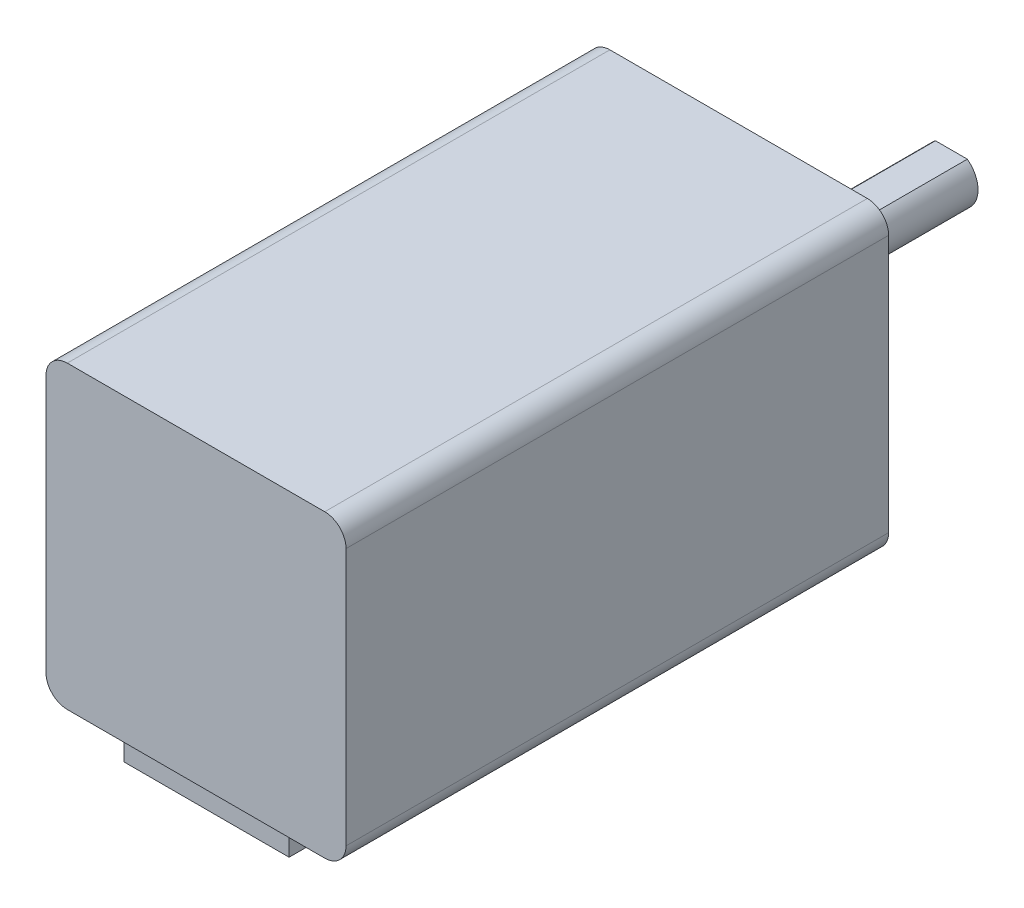
SolidWorks part; units mm, degrees
ref_plane "前视基准面" through (0, 0, 0) normal (0, 0, 1) x (1, 0, 0)
ref_plane "上视基准面" through (0, 0, 0) normal (0, 1, 0) x (1, 0, 0)
ref_plane "右视基准面" through (0, 0, 0) normal (1, 0, 0) x (0, 0, -1)
sketch "草图1" plane through (0, 0, 0) normal (0, 0, 1) x (1, 0, 0)
  line L0 (0, 0) -> (-46.9688, 0) construction
  line L1 (0, 0) -> (46.2703, 0) construction
  line L2 (0, 0) -> (0, -44.5864) construction
  line L3 (0, 0) -> (0, 48.8523) construction
  line L4 (-12.1, -14.1) -> (12.1, -14.1)
  line L5 (-14.1, -12.1) -> (-14.1, 12.1)
  line L6 (-12.1, 14.1) -> (12.1, 14.1)
  line L7 (14.1, -12.1) -> (14.1, 12.1)
  circle A0 centre (-11.5, 11.5) radius 1.25
  circle A1 centre (11.5, 11.5) radius 1.25
  circle A2 centre (-11.5, -11.5) radius 1.25
  circle A3 centre (11.5, -11.5) radius 1.25
  arc A4 (-12.1, -14.1) -> (-14.1, -12.1) centre (-12.1, -12.1) cw
  arc A5 (12.1, -14.1) -> (14.1, -12.1) centre (12.1, -12.1) ccw
  arc A6 (14.1, 12.1) -> (12.1, 14.1) centre (12.1, 12.1) ccw
  arc A7 (-14.1, 12.1) -> (-12.1, 14.1) centre (-12.1, 12.1) cw
  point P9 (14.1, 0)
  point P10 (-14.1, 0)
  point P11 (0, 14.1)
  point P12 (0, -14.1)
  point P23 (-14.1, -14.1)
  point P26 (14.1, -14.1)
  point P29 (14.1, 14.1)
  point P32 (-14.1, 14.1)
  dimension "D1" = 2
extrude "凸台-拉伸2" add sketch "草图1" along normal blind 51 contours A1 | A7 L5 A4 L4 A5 L7 A6 L6 A3 A1 A0 A2 | A2 | A3 | A0 region at (0, 0, 0) region at (11.5, 11.5, 0) region at (-11.5, -11.5, 0) region at (11.5, -11.5, 0)
hole_wizard "M2.5 螺纹孔1" positions "草图4" profile "草图5" tap size "M2.5" standard "GB"
sketch "草图4" plane through (0, 0, 0) normal (0, 0, -1) x (-1, 0, 0)
  point P0 (-11.5, 11.5)
  point P3 (11.5, 11.5)
  point P6 (11.5, -11.5)
  point P9 (-11.5, -11.5)
sketch "草图5" plane through (11.5, 11.5, 0) normal (1, 0, 0) x (0, 1, 0)
  line L0 (0, 0) -> (0, 5.3659)
  line L1 (0, 5.3659) -> (1.025, 4.75)
  line L2 (1.025, 4.75) -> (1.025, 0)
  line L5 (1.025, 0) -> (0, 0)
  line L10 (0, 5.3659) -> (-1.025, 4.75) construction
  line L11 (0, -6.35) -> (0, 107.95) construction
  dimension "螺纹孔钻头直径" = 2.05
  dimension "螺纹孔钻头深度" = 4.75
  dimension "导头角度" = 118
cosmetic thread "孔螺蚊线1" parameters "D1"=2.5, "D2"=2.5
cosmetic thread "孔螺蚊线2" parameters "D1"=2.5, "D2"=2.5
cosmetic thread "孔螺蚊线3" parameters "D1"=2.5, "D2"=2.5
cosmetic thread "孔螺蚊线4" parameters "D1"=2.5, "D2"=2.5
sketch "草图7" plane through (0, 0, 0) normal (0, 0, 1) x (1, 0, 0)
  circle A0 centre (0, 0) radius 11
  circle A1 centre (0, 0) radius 2.5
extrude "凸台-拉伸3" add sketch "草图7" against normal blind 2
extrude "凸台-拉伸4" add sketch "草图7<2>" against normal blind 20 contours A1 region at (0, 0, 0)
sketch "草图7<2>" plane through (0, 0, 0) normal (0, 0, 1) x (1, 0, 0) same geometry as "草图7"
sketch "草图8" plane through (0, 0, 0) normal (1, 0, 0) x (0, 0, -1)
  line L0 (20, 2.5) -> (20, 2)
  line L1 (20, 2) -> (5, 2)
  line L2 (5, 2) -> (5, 2.5)
  line L3 (5, 2.5) -> (20, 2.5)
extrude "切除-拉伸1" cut sketch "草图8" against normal mid plane 3
ref_plane "基准面1" through (0, 0, 44) normal (0, 0, 1) x (1, 0, 0)
sketch "草图9" plane through (0, 0, 44) normal (0, 0, 1) x (1, 0, 0)
  line L0 (0, 0) -> (0, -17.8822) construction
  line L1 (7.75, -14.1) -> (-7.75, -14.1)
  line L2 (-7.75, -16.7) -> (7.75, -16.7)
  line L3 (-7.75, -14.1) -> (-7.75, -16.7)
  line L4 (7.75, -14.1) -> (7.75, -16.7)
  point P4 (0, -14.1)
  point P8 (0, -16.7)
extrude "凸台-拉伸5" add sketch "草图9" along normal blind 6
